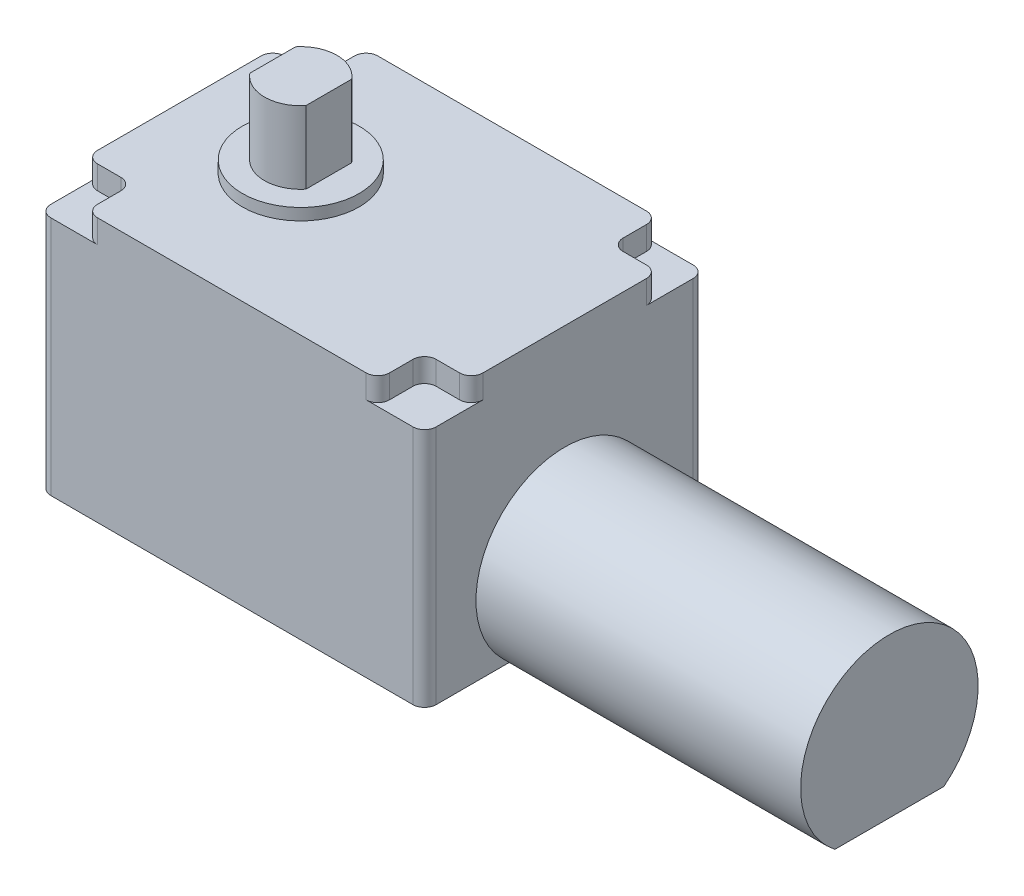
SolidWorks part; units mm, degrees
material "ABS"
ref_plane "Front Plane" through (0, 0, 0) normal (0, 0, 1) x (1, 0, 0)
ref_plane "Top Plane" through (0, 0, 0) normal (0, 1, 0) x (1, 0, 0)
ref_plane "Right Plane" through (0, 0, 0) normal (1, 0, 0) x (0, 0, -1)
ref_axis "x-axis" through (88.99, 0, 0) along (-1, 0, 0)
ref_axis "y-axis" through (0, 0, 55) along (0, 0, -1)
ref_axis "z-axis" through (0, 55, 0) along (0, -1, 0)
sketch "Sketch1" plane through (0, 0, 0) normal (0, 1, 0) x (1, 0, 0)
  line L0 (-5.2, 0) -> (11.3, 0) construction
  line L1 (-5.2, 6) -> (11.3, 6)
  line L2 (-5.2, 6) -> (-5.2, -6)
  line L3 (-5.2, -6) -> (11.3, -6)
  line L4 (11.3, 6) -> (11.3, -6)
  dimension "D1" = 5.2
  dimension "D2" = 12
  dimension "D3" = 16.5
extrude "gearbox" add sketch "Sketch1" against normal blind 11.3
sketch "Sketch2" plane through (0, 0, 0) normal (0, 1, 0) x (1, 0, 0)
  circle A0 centre (0, 0) radius 2.5
  dimension "D1" = 5
extrude "shaftbase" add sketch "Sketch2" along normal blind 0.5
sketch "Sketch3" plane through (0, 0.5, 0) normal (0, 1, 0) x (1, 0, 0)
  line L0 (-1.2, 0.9811) -> (-1.2, -0.9811)
  line L1 (1.2, 0.9811) -> (1.2, -0.9811)
  arc A0 (-1.2, -0.9811) -> (1.2, -0.9811) centre (0, 0) ccw
  arc A1 (1.2, 0.9811) -> (-1.2, 0.9811) centre (0, 0) ccw
  dimension "D1" = 1.55
  dimension "D2" = 2.4
extrude "shaft" add sketch "Sketch3" along normal blind 3.1
sketch "Sketch4" plane through (11.3, 0, 0) normal (1, 0, 0) x (0, 0, -1)
  line L0 (0, 0) -> (0, -11.3) construction
  line L1 (-6, -11.3) -> (6, -11.3) construction
  line L2 (2.3324, -11.3) -> (-2.3324, -11.3)
  arc A0 (2.3324, -11.3) -> (-2.3324, -11.3) centre (0, -8.3) ccw
  dimension "D1" = 7.6
  dimension "D2" = 3
extrude "motor" add sketch "Sketch4" along normal offset from surface (13.9 mm away) 30.4 up to face at (-5.2, -5.65, 0)
sketch "Sketch5" plane through (0, 0, 0) normal (0, 1, 0) x (1, 0, 0)
  line L0 (11.3, 6) -> (-5.2, 6) construction
  line L1 (-5.2, 6) -> (-3.2, 6)
  line L2 (-5.2, 6) -> (-5.2, 4)
  line L3 (-5.2, 4) -> (-3.2, 4)
  line L4 (-3.2, 6) -> (-3.2, 4)
  line L5 (11.3, 6) -> (9.3, 6)
  line L6 (11.3, 6) -> (11.3, 4)
  line L7 (11.3, 4) -> (9.3, 4)
  line L8 (9.3, 6) -> (9.3, 4)
  line L9 (-5.2, -6) -> (11.3, -6) construction
  line L10 (11.3, -6) -> (9.3, -6)
  line L11 (11.3, -6) -> (11.3, -4)
  line L12 (11.3, -4) -> (9.3, -4)
  line L13 (9.3, -6) -> (9.3, -4)
  line L14 (-5.2, -6) -> (-3.2, -6)
  line L15 (-5.2, -6) -> (-5.2, -4)
  line L16 (-5.2, -4) -> (-3.2, -4)
  line L17 (-3.2, -6) -> (-3.2, -4)
  line L18 (-5.2, 6) -> (-5.2, -6) construction
  line L19 (11.3, -6) -> (11.3, 6) construction
  dimension "D1" = 2
  dimension "D2" = 2
extrude "screwinsets" cut sketch "Sketch5" against normal blind 1
sketch "Sketch6" plane through (0, -11.3, 0) normal (0, -1, 0) x (1, 0, 0)
  line L0 (0, 0) -> (5, 0) construction
  circle A0 centre (5, 0) radius 1.25
  dimension "D1" = 2.5
  dimension "D2" = 5
extrude "backextrusion" add sketch "Sketch6" along normal offset from surface (0.6 mm away) 12.4 up to face at (0, 0.5, 2.5)
fillet "fillets" radius 0.5 16 edges at (-3.2, -0.5, -6) (-5.2, -0.5, -4) (-5.2, -0.5, 4) (-3.2, -0.5, 6) (9.3, -0.5, -6) (11.3, -0.5, -4) (11.3, -0.5, 4) (9.3, -0.5, 6) (-3.2, -0.5, -4) (9.3, -0.5, 4) (9.3, -0.5, -4) (-3.2, -0.5, 4) (-5.2, -6.15, -6) (-5.2, -6.15, 6) (11.3, -6.15, -6) (11.3, -6.15, 6)
